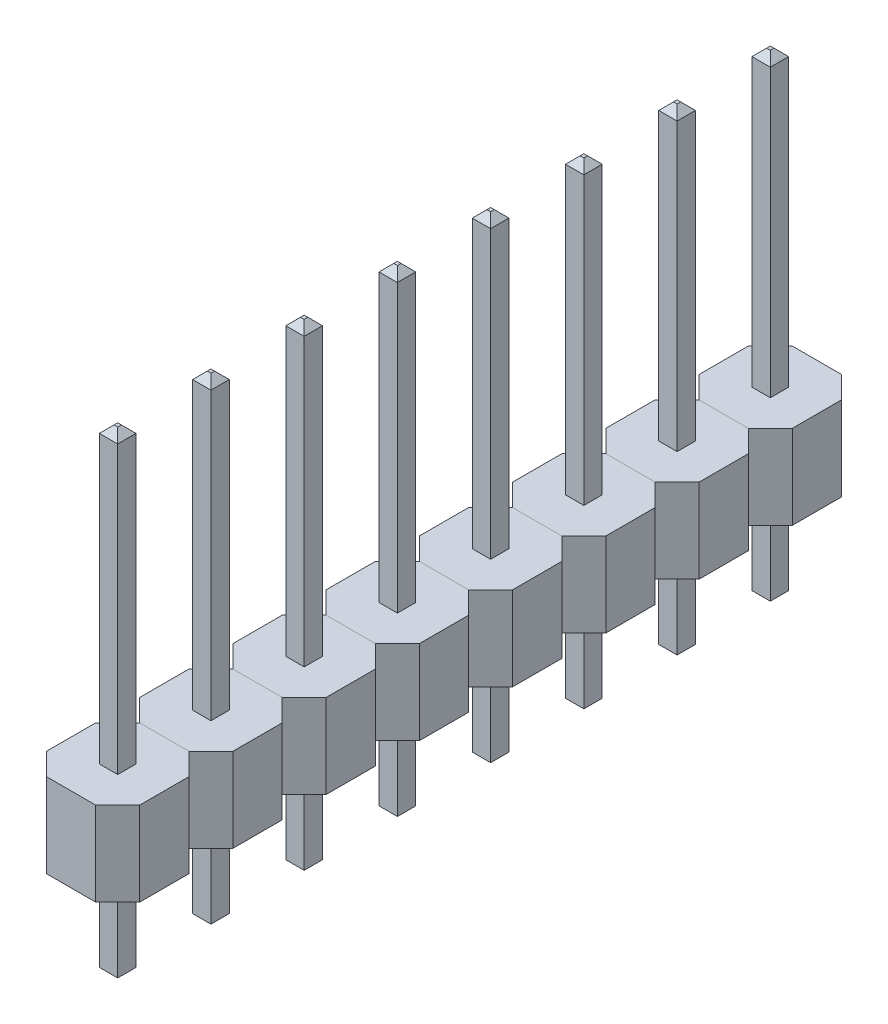
SolidWorks part; units mm, degrees
ref_plane "Front Plane" through (0, 0, 0) normal (0, 0, 1) x (1, 0, 0)
ref_plane "Top Plane" through (0, 0, 0) normal (0, 1, 0) x (1, 0, 0)
ref_plane "Right Plane" through (0, 0, 0) normal (1, 0, 0) x (0, 0, -1)
sketch "Sketch1" plane through (0, 0, 0) normal (0, 1, 0) x (1, 0, 0)
  line L1 (-1.27, 1.27) -> (1.27, 1.27)
  line L2 (-1.27, 1.27) -> (-1.27, -1.27)
  line L3 (-1.27, -1.27) -> (1.27, -1.27)
  line L4 (1.27, 1.27) -> (1.27, -1.27)
  line L5 (-1.27, 1.27) -> (1.27, -1.27) construction
  line L6 (-1.27, -1.27) -> (1.27, 1.27) construction
  point P0 (0, 0)
  dimension "D1" = 2.54
  dimension "D2" = 2.54
extrude "Boss-Extrude1" add sketch "Sketch1" along normal blind 2.29
chamfer "Chamfer1" distance 0.6 4 edges at (-1.27, 1.145, -1.27) (1.27, 1.145, -1.27) (1.27, 1.145, 1.27) (-1.27, 1.145, 1.27)
sketch "Sketch2" plane through (0, 2.29, 0) normal (0, 1, 0) x (1, 0, 0)
  line L1 (-0.25, 0.25) -> (0.25, 0.25)
  line L2 (-0.25, 0.25) -> (-0.25, -0.25)
  line L3 (-0.25, -0.25) -> (0.25, -0.25)
  line L4 (0.25, 0.25) -> (0.25, -0.25)
  line L5 (-0.25, 0.25) -> (0.25, -0.25) construction
  line L6 (-0.25, -0.25) -> (0.25, 0.25) construction
  point P0 (0, 0)
  dimension "D2" = 0.5
extrude "Boss-Extrude2" add sketch "Sketch2" along normal blind 8 and the other way blind 5
chamfer "Chamfer2" distance 0.2 8 edges at (0, 10.29, 0.25) (-0.25, 10.29, 0) (0, 10.29, -0.25) (0.25, 10.29, 0) (0, -2.71, -0.25) (-0.25, -2.71, 0) (0, -2.71, 0.25) (0.25, -2.71, 0)
ref_axis "Ось1" through (0, -3.4193, 0) along (0, 1, 0)
pattern_linear "Линейный массив2" count 8 spacing 2.54 along (0, 0, 1) of bodies 102
